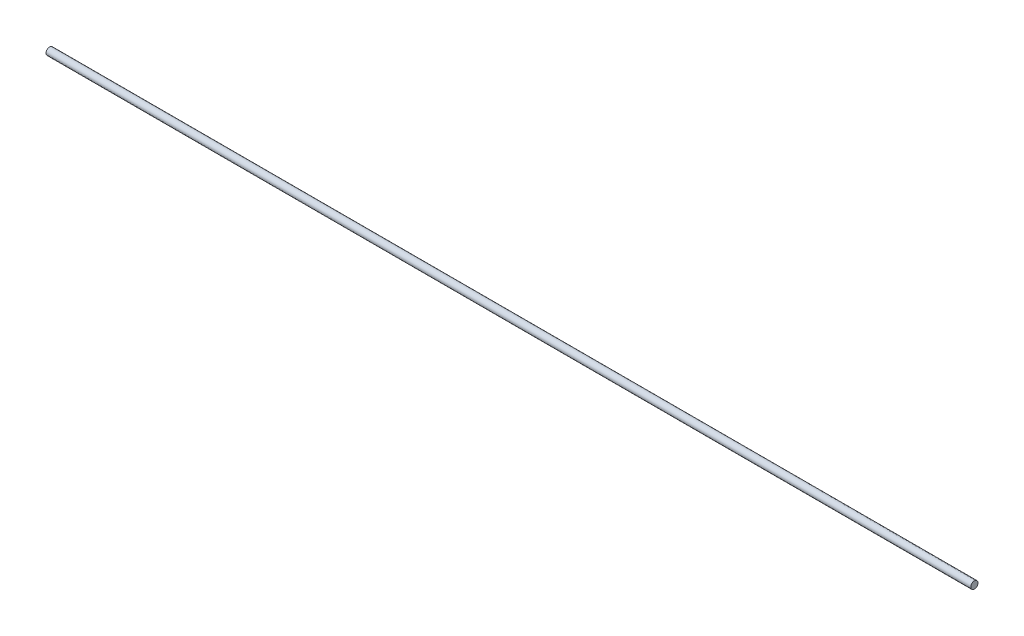
SolidWorks part; units mm, degrees
material "Hexcel AS4C (3000 Filaments)"
ref_plane "Front Plane" through (0, 0, 0) normal (0, 0, 1) x (1, 0, 0)
ref_plane "Top Plane" through (0, 0, 0) normal (0, 1, 0) x (1, 0, 0)
ref_plane "Right Plane" through (0, 0, 0) normal (1, 0, 0) x (0, 0, -1)
sketch "Sketch1" plane through (0, 0, 0) normal (1, 0, 0) x (0, 0, -1)
  circle A0 centre (5.918, 4.7962) radius 3.175 construction
  circle A1 centre (5.918, 4.7962) radius 3.175
extrude "Boss-Extrude1" add sketch "Sketch1" along normal blind 812.8 contours A1
